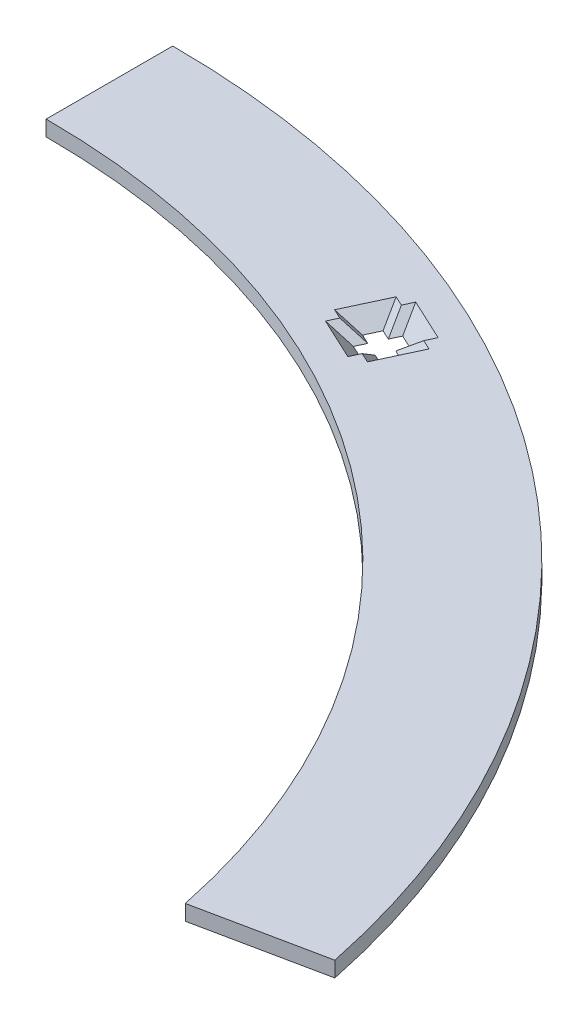
SolidWorks part; units mm, degrees
ref_plane "Front Plane" through (0, 0, 0) normal (0, 0, 1) x (1, 0, 0)
ref_plane "Top Plane" through (0, 0, 0) normal (0, 1, 0) x (1, 0, 0)
ref_plane "Right Plane" through (0, 0, 0) normal (1, 0, 0) x (0, 0, -1)
sketch "Sketch1" plane through (0, 0, 0) normal (0, 1, 0) x (1, 0, 0)
  line L0 (0, 49.519) -> (0, 59.7644)
  line L1 (48.4915, 10.0354) -> (58.5242, 12.1117)
  arc A0 (0, 49.519) -> (48.4915, 10.0354) centre (0, 0) cw
  arc A1 (0, 59.7644) -> (58.5242, 12.1117) centre (0, 0) cw
  dimension "D3" = 10.2453
  dimension "D4" = 59.7644
  dimension "D1" = 67.6789
  dimension "D2" = 81.6814
extrude "Boss-Extrude1" add sketch "Sketch1" along normal blind 1
sketch "Sketch3" plane through (0, 1, 0) normal (0, 1, 0) x (1, 0, 0)
  circle A0 centre (0, 0) radius 57.7153
  arc A1 (58.5242, 12.1117) -> (0, 59.7644) centre (0, 0) ccw construction
  line M15 (48.4915, 10.0354) -> (58.5242, 12.1117)
  arc M16 (58.5242, 12.1117) -> (0, 59.7644) centre (0, 0) ccw
  line M17 (0, 59.7644) -> (0, 49.519)
  dimension "D1" = 2.0491
extrude "Cut-Extrude2" cut sketch "Sketch3" against normal through all contours A0 M15 M16 M17 region at (36.9198, 1, -45.3428)
sketch "Sketch2" plane through (0, 1, 0) normal (0, 1, 0) x (1, 0, 0)
  line L0 (20.9276, 44.8795) -> (24.3915, 52.3078)
  line L1 (19.7397, 45.4334) -> (56.979, 28.0685) construction
  line L2 (0, 57.7153) -> (0, 49.519) construction
  line L3 (22.7136, 49.8925) -> (21.6993, 47.7174)
  line L4 (22.2064, 48.805) -> (23.1127, 48.3823)
  line L5 (22.6056, 47.2948) -> (23.6199, 49.4699)
  line L6 (23.6199, 49.4699) -> (22.7136, 49.8925)
  line L7 (22.6056, 47.2948) -> (21.6993, 47.7174)
  line L8 (22.6596, 48.5937) -> (47007.2906, 17149.6008) construction
  line L9 (21.7833, 49.5539) -> (21.3607, 48.6476)
  line L10 (23.5359, 47.6334) -> (21.3607, 48.6476)
  line L11 (21.7833, 49.5539) -> (23.9585, 48.5397)
  line L12 (23.9585, 48.5397) -> (23.5359, 47.6334)
  arc A1 (48.4915, 10.0354) -> (0, 49.519) centre (0, 0) ccw construction
  arc A3 (56.5177, 11.6965) -> (0, 57.7153) centre (0, 0) ccw construction
  point P7 (0, 0)
  point P10 (22.6596, 48.5937)
  dimension "D2" = 1.2
  dimension "D1" = 25
  dimension "D3" = 1
  dimension "D4" = 45
extrude "Cut-Extrude1" cut sketch "Sketch2" against normal through all contours L0 L11 L5 L6 | L3 L11 L0 L6 | L11 L3 L4 L0 | L11 L9 L10 L3 | L10 L0 L4 L3 | L0 L10 L3 L7 | L5 L10 L0 L7 | L10 L5 L4 L0 | L12 L11 L5 L10 | L11 L0 L4 L5 region at (22.0738, 1, -47.9289) region at (22.5269, 1, -47.7176) region at (22.3274, 1, -48.4727) region at (22.7805, 1, -48.2614) region at (22.5387, 1, -48.9259) region at (22.9918, 1, -48.7146) region at (23.43, 1, -48.2344) region at (21.8892, 1, -48.9529) region at (22.7922, 1, -49.4697) region at (23.2454, 1, -49.2584)
chamfer "Chamfer1" distance 1 angle 45 12 edges at (21.8472, 1, -48.0346) (22.1524, 1, -47.5061) (22.7535, 1, -47.612) (23.2186, 1, -47.7813) (23.7472, 1, -48.0865) (23.6413, 1, -48.6876) (23.472, 1, -49.1527) (23.1667, 1, -49.6812) (22.5657, 1, -49.5753) (22.1005, 1, -49.406) (21.572, 1, -49.1008) (21.6779, 1, -48.4997)
equation "\"outer_diameter\"= 26mm"
equation "\"D2@Sketch1\"= \"outer_diameter\" * pi"
equation "\"inner diameter\"= 21.54285714mm"
equation "\"D1@Sketch1\"= \"inner diameter\" * pi"
equation "\"D4@Sketch1\" = \"outer_diameter\" / ( 2 * sin ( 12.5634694 ) )"
equation "\"height\"= 10"
equation "\"D3@Sketch1\" = \"height\" / cos ( 12.5634694 )"
equation "\"D1@Sketch3\"= 2 / cos ( 12.5634694 )"
